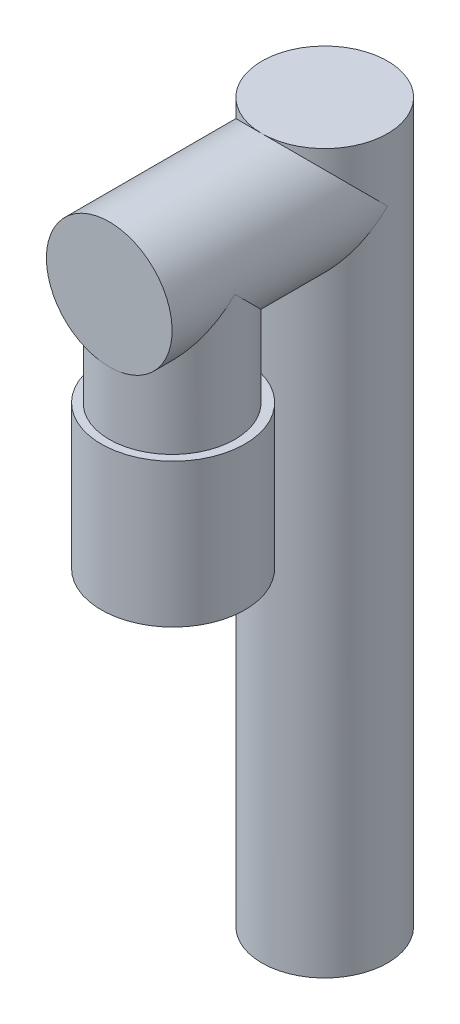
SolidWorks part; units mm, degrees
ref_plane "Front Plane" through (0, 0, 0) normal (0, 0, 1) x (1, 0, 0)
ref_plane "Top Plane" through (0, 0, 0) normal (0, 1, 0) x (1, 0, 0)
ref_plane "Right Plane" through (0, 0, 0) normal (1, 0, 0) x (0, 0, -1)
sketch "Sketch1" plane through (0, 0, 0) normal (0, 1, 0) x (1, 0, 0)
  circle A0 centre (0, 0) radius 3.5
extrude "Boss-Extrude1" add sketch "Sketch1" along normal blind 40
sketch "Sketch2" plane through (0, 0, 0) normal (0, 0, 1) x (1, 0, 0)
  line L0 (3.5, 40) -> (-3.5, 40) construction
  circle A0 centre (0, 36.5) radius 3.5
  dimension "D1" = 3.5
extrude "Boss-Extrude2" add sketch "Sketch2" along normal blind 12
ref_plane "Plane1" through (0, 36.5, 0) normal (0, 1, 0) x (1, 0, 0)
sketch "Sketch3" plane through (0, 36.5, 0) normal (0, 1, 0) x (1, 0, 0)
  line L0 (-3.5, -12) -> (3.5, -12) construction
  circle A0 centre (0, -8.5) radius 3.5
  dimension "D1" = 3.5
extrude "Boss-Extrude3" add sketch "Sketch3" against normal blind 7
sketch "Sketch4" plane through (0, 29.5, 0) normal (0, -1, 0) x (1, 0, 0)
  circle A0 centre (0, 8.4449) radius 4
  circle A1 centre (0, 8.4449) radius 1
extrude "Boss-Extrude4" add sketch "Sketch4" along normal blind 8
